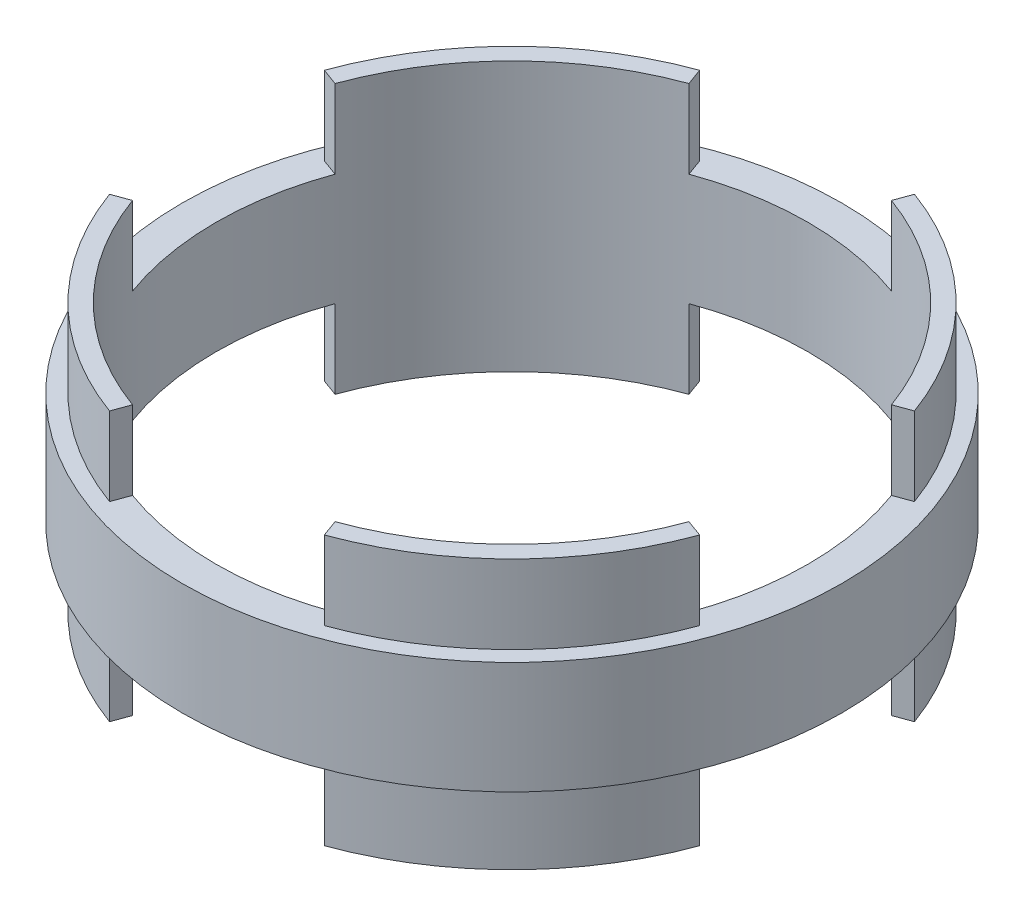
SolidWorks part; units mm, degrees
ref_plane "Front Plane" through (0, 0, 0) normal (0, 0, 1) x (1, 0, 0)
ref_plane "Top Plane" through (0, 0, 0) normal (0, 1, 0) x (1, 0, 0)
ref_plane "Right Plane" through (0, 0, 0) normal (1, 0, 0) x (0, 0, -1)
sketch "Sketch1" plane through (0, 0, 0) normal (0, 1, 0) x (1, 0, 0)
  circle A0 centre (0, 0) radius 93.345
  circle A1 centre (0, 0) radius 83.82
  dimension "D1" = 186.69
  dimension "D2" = 167.64
extrude "Boss-Extrude1" add sketch "Sketch1" along normal mid plane 31.75
sketch "Sketch2" plane through (0, 0, 0) normal (0, 1, 0) x (1, 0, 0)
  circle A0 centre (0, 0) radius 88.9
  circle A1 centre (0, 0) radius 83.82
  dimension "D1" = 177.8
  dimension "D2" = 167.64
extrude "Boss-Extrude2" add sketch "Sketch2" along normal mid plane 76.2
sketch "Sketch3" plane through (0, 0, 0) normal (0, 1, 0) x (1, 0, 0)
  line L0 (0, -116.3805) -> (0, 112.0878) construction
  line L1 (-120.9117, 0) -> (128.5432, 0) construction
  line L2 (0, 0) -> (-30.4056, 83.5387)
  line L3 (0, 0) -> (30.4056, 83.5387)
  circle A5 centre (0, 0) radius 88.9 construction
  circle A6 centre (0, 0) radius 88.9 construction
  arc A7 (-30.4056, 83.5387) -> (30.4056, 83.5387) centre (0, 0) cw
  dimension "D1" = 20
  dimension "D2" = 20
extrude "Cut-Extrude1" cut sketch "Sketch3" against normal mid plane 76.2
pattern_circular "CirPattern1" count 4 over 360 about axis through (0, 38.1, 0) along (0, -1, 0) of "Cut-Extrude1" reverse direction yes
sketch "Sketch4" plane through (0, 0, 0) normal (0, 1, 0) x (1, 0, 0)
  circle A0 centre (0, 0) radius 88.9
  circle A1 centre (0, 0) radius 83.82
extrude "Boss-Extrude3" add sketch "Sketch4" along normal mid plane 31.75
